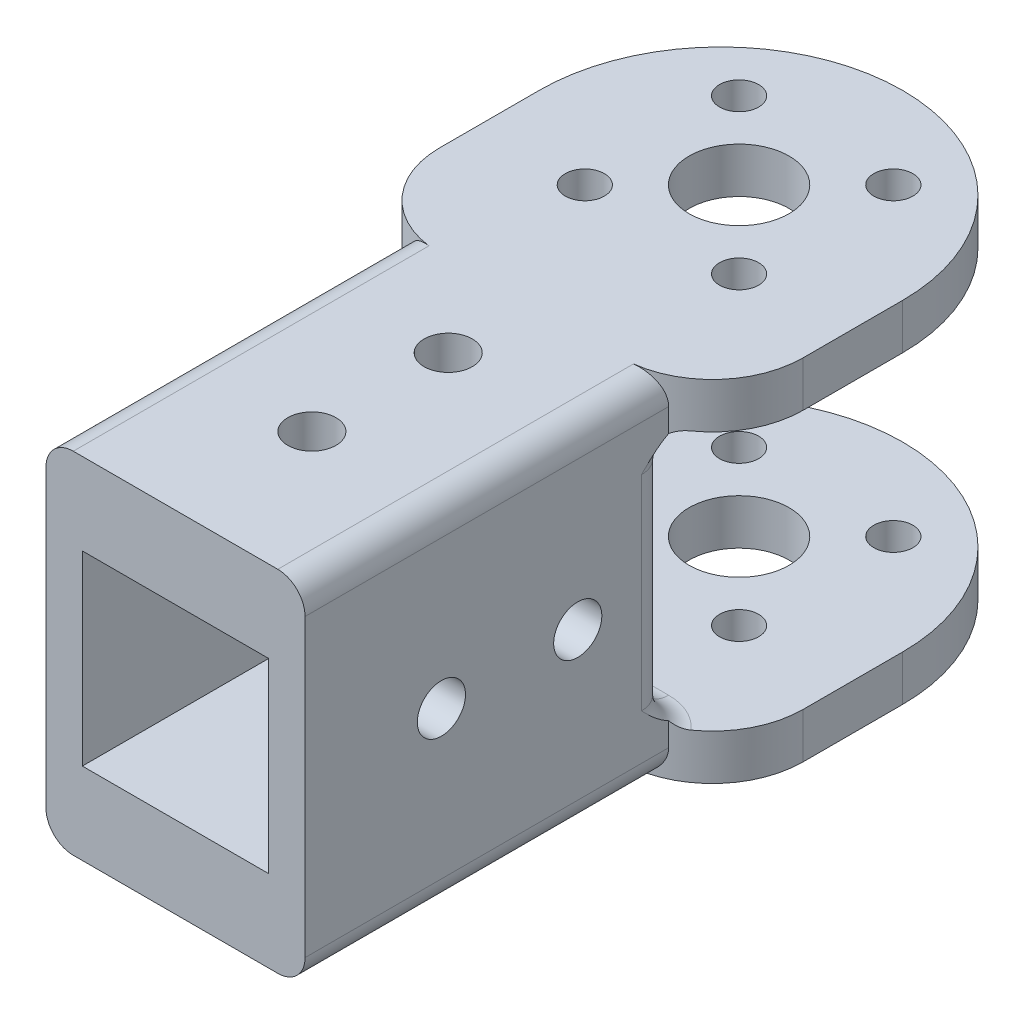
SolidWorks part; units mm, degrees
ref_plane "前视基准面" through (0, 0, 0) normal (0, 0, 1) x (1, 0, 0)
ref_plane "上视基准面" through (0, 0, 0) normal (0, 1, 0) x (1, 0, 0)
ref_plane "右视基准面" through (0, 0, 0) normal (1, 0, 0) x (0, 0, -1)
other "Configuration Table"
sketch "草图1" plane through (0, 0, 0) normal (0, 1, 0) x (1, 0, 0)
  circle A0 centre (0, 0) radius 17.5
  dimension "D1" = 35
extrude "凸台-拉伸4" add sketch "草图1" along normal blind 6
sketch "草图4" plane through (0, 6, 0) normal (0, 1, 0) x (1, 0, 0)
  line L1 (-20, -20) -> (20, -20)
  line L2 (-20, -20) -> (-20, 20)
  line L3 (-20, 20) -> (20, 20)
  line L4 (20, -20) -> (20, 20)
  line L5 (-20, -20) -> (20, 20) construction
  line L6 (-20, 20) -> (20, -20) construction
  point P0 (0, 0)
  dimension "D1" = 40
  dimension "D2" = 40
extrude "凸台-拉伸5" add sketch "草图4" along normal blind 30
fillet "圆角1" radius 5 1 edges at (0, 6, 17.5)
sketch "草图5" plane through (0, 0, 20) normal (0, 0, 1) x (1, 0, 0)
  line L0 (-1020, 21) -> (48980, 21) construction
  line L1 (-20, 36) -> (-20, 6) construction
  line L2 (0, -994) -> (0, 49006) construction
  line L3 (-10.3078, 6) -> (10.3078, 6) construction
  line L4 (-14.25, 35.25) -> (14.25, 35.25)
  line L5 (-10.25, 10.75) -> (10.25, 10.75)
  line L6 (-10.25, 10.75) -> (-10.25, 31.25)
  line L7 (-10.25, 31.25) -> (10.25, 31.25)
  line L8 (10.25, 10.75) -> (10.25, 31.25)
  line L9 (-10.25, 10.75) -> (10.25, 31.25) construction
  line L10 (-10.25, 31.25) -> (10.25, 10.75) construction
  line L11 (14.25, 6.75) -> (14.25, 35.25)
  line L12 (-14.25, 6.75) -> (14.25, 6.75)
  line L13 (-14.25, 6.75) -> (-14.25, 35.25)
  point P5 (-20, 21)
  point P6 (0, 21)
  point P10 (0, 6)
  dimension "D1" = 20.5
  dimension "D2" = 20.5
  dimension "D3" = 4
extrude "凸台-拉伸7" add sketch "草图5" along normal blind 40
sketch "草图7" plane through (0, 6.75, 0) normal (0, -1, 0) x (1, 0, 0)
  line L0 (0, 60) -> (0, 45)
  line L1 (-14.25, 60) -> (14.25, 60) construction
  line L2 (0, 45) -> (0, 30)
  circle A0 centre (0, 45) radius 2.65
  circle A1 centre (0, 30) radius 2.65
  dimension "D2" = 5.3
  dimension "D4" = 5.3
  dimension "D1" = 15
  dimension "D3" = 15
extrude "切除-拉伸1" cut sketch "草图7" against normal through all contours A1 | A0 region at (1.8208, 6.75, 31.8208)
sketch "草图8" plane through (14.25, 0, 0) normal (1, 0, 0) x (0, 0, -1)
  line L0 (-60, 21) -> (-45, 21)
  line L1 (-60, 6.75) -> (-60, 35.25) construction
  line L2 (-45, 21) -> (-30, 21)
  circle A0 centre (-45, 21) radius 2.65
  circle A1 centre (-30, 21) radius 2.65
  dimension "D2" = 5.3
  dimension "D4" = 5.3
  dimension "D1" = 15
  dimension "D3" = 15
extrude "切除-拉伸2" cut sketch "草图8" against normal through all contours L0 A0 L2 | A1 | A0 region at (14.25, 19.8753, 45)
sketch "草图26" plane through (0, 0, 0) normal (0, -1, 0) x (1, 0, 0)
  circle A0 centre (0, 0) radius 22.5
extrude "切除-拉伸15" cut sketch "草图26" against normal blind 6
sketch "草图27" plane through (0, 6, 0) normal (0, -1, 0) x (1, 0, 0)
  circle A0 centre (0, 0) radius 15
  dimension "D1" = 30
extrude "切除-拉伸16" cut sketch "草图27" against normal through all
sketch "草图28" plane through (0, 36, 0) normal (0, 1, 0) x (1, 0, 0)
  line L1 (-20, 20) -> (20, 20)
  line L2 (-20, 20) -> (-20, -20)
  line L3 (-20, -20) -> (20, -20)
  line L4 (20, 20) -> (20, -20)
extrude "切除-拉伸17" cut sketch "草图28" against normal blind 5
sketch "草图29" plane through (0, 6, 0) normal (0, -1, 0) x (1, 0, 0)
  line L1 (-20, 20) -> (20, 20)
  line L2 (-20, 20) -> (-20, -20)
  line L3 (-20, -20) -> (20, -20)
  line L4 (20, 20) -> (20, -20)
extrude "切除-拉伸18" cut sketch "草图29" against normal blind 5
sketch "草图30" plane through (0, 0, 20) normal (0, 0, -1) x (-1, 0, 0)
  line L1 (-14.25, 35.25) -> (14.25, 35.25)
  line L2 (-14.25, 35.25) -> (-14.25, 6.75)
  line L3 (-14.25, 6.75) -> (14.25, 6.75)
  line L4 (14.25, 35.25) -> (14.25, 6.75)
extrude "凸台-拉伸11" add sketch "草图30" against normal blind 5
sketch "草图31" plane through (0, 11, 0) normal (0, -1, 0) x (1, 0, 0)
  line L0 (0, 0) -> (0, -18)
  line L1 (0, -18) -> (8.3107, -12.4873)
  line L2 (8.3107, -12.4873) -> (-8.3107, -12.4873)
  line L3 (-8.3107, -12.4873) -> (0, -18)
  circle A0 centre (0, 0) radius 15 construction
  circle M8 centre (0, 0) radius 15
  dimension "D1" = 18
extrude "切除-拉伸19" cut sketch "草图31" against normal through all contours L3 L0 M8 | L0 L1 M8 region at (2.7702, 11, -14.3248) region at (-2.1466, 11, -15.6634)
fillet "圆角6" radius 20 4 edges at (-20, 21, -20) (20, 21, -20) (20, 21, 20) (-20, 21, 20)
ref_plane "基准面1" through (0, 21, 0) normal (0, 1, 0) x (1, 0, 0)
sketch "草图33" plane through (0, 21, 0) normal (0, 1, 0) x (1, 0, 0)
  circle A0 centre (0, 0) radius 20
  circle A1 centre (0, 0) radius 12.5
  dimension "D1" = 25
extrude "凸台-拉伸14" add sketch "草图33" along normal mid plane 2
sketch "草图36" plane through (0, 35.25, 0) normal (0, 1, 0) x (1, 0, 0)
  line L0 (14.25, -20) -> (-14.25, -20) construction
  line L1 (-14.25, -20) -> (14.25, -20)
  line L2 (-14.25, -20) -> (-14.25, -60)
  line L3 (-14.25, -60) -> (14.25, -60)
  line L4 (14.25, -20) -> (14.25, -60)
  line L5 (-14.25, -20) -> (14.25, -20) construction
  circle A0 centre (0, -30) radius 2.65
  circle A1 centre (0, -45) radius 2.65
extrude "凸台-拉伸15" add sketch "草图36" along normal mid plane 10
mirror "镜向1" about plane through (0, 21, 0) normal (0, 1, 0) of "凸台-拉伸15"
sketch "草图38" plane through (0, 0, 20) normal (0, 0, -1) x (-1, 0, 0)
  line L5 (-14.25, 40.25) -> (14.25, 40.25) construction
  line L6 (-20, 35.25) -> (20, 35.25)
  line L7 (-20, 35.25) -> (-20, 45.25)
  line L8 (-20, 45.25) -> (20, 45.25)
  line L9 (20, 35.25) -> (20, 45.25)
  line L10 (-20, 35.25) -> (20, 45.25) construction
  line L11 (-20, 45.25) -> (20, 35.25) construction
  line L12 (-1020, 40.25) -> (48980, 40.25)
  line L13 (-20, 40.25) -> (20, 40.25)
  point P0 (0, 40.25)
  point P10 (-20, 40.25)
  dimension "D1" = 10
  dimension "D2" = 40
extrude "凸台-拉伸16" add sketch "草图38" along normal blind 40 contours L12 L7 L6 L9 region at (0, 37.75, 20)
sketch "草图39" plane through (0, 11, 0) normal (0, -1, 0) x (1, 0, 0)
  line L1 (-20, -20) -> (20, -20)
  line L2 (-20, -20) -> (-20, 20)
  line L3 (-20, 20) -> (20, 20)
  line L4 (20, -20) -> (20, 20)
extrude "切除-拉伸20" cut sketch "草图39" against normal blind 20
mirror "镜向2" about plane through (0, 21, 0) normal (0, 1, 0) of "凸台-拉伸16"
sketch "草图40" plane through (0, 40.25, 0) normal (0, 1, 0) x (1, 0, 0)
  line L0 (0, 0) -> (0, 2)
  line L1 (-1000, 2) -> (49000, 2) construction
  line L2 (0, 2) -> (35355.3391, -35353.3391) construction
  circle A6 centre (0, 2) radius 5.5
  circle A8 centre (-8.4853, 10.4853) radius 2.15
  circle A9 centre (8.4853, 10.4853) radius 2.15
  circle A10 centre (8.4853, -6.4853) radius 2.15
  circle A11 centre (-8.4853, -6.4853) radius 2.15
  point P18 (0, 0)
  dimension "D1" = 2
  dimension "D5" = 4.3
  dimension "D6" = 4
  dimension "D2" = 11
  dimension "D4" = 45
extrude "切除-拉伸22" cut sketch "草图40" against normal through all contours A6 | A8 | A9 | A10 | A11 region at (-5.3444, 40.25, -2) region at (-8.4853, 40.25, -10.4853) region at (8.4853, 40.25, -10.4853) region at (8.4853, 40.25, 6.4853)
fillet "圆角11" radius 10 4 edges at (-20, 37.75, 20) (20, 37.75, 20) (20, 4.25, 20) (-20, 4.25, 20)
fillet "圆角12" radius 20 4 edges at (20, 4.25, -20) (-20, 4.25, -20) (-20, 37.75, -20) (20, 37.75, -20)
fillet "圆角13" radius 3 6 edges at (14.25, 21, 20) (-14.25, 21, 20) (-14.25, 40.25, 40) (14.25, 40.25, 40) (14.25, 1.75, 40) (-14.25, 1.75, 40)
fillet "圆角14" radius 3 6 edges at (13.3713, 6.75, 20.8787) (-13.3713, 6.75, 20.8787) (13.3713, 35.25, 20.8787) (-13.3713, 35.25, 20.8787) (0, 6.75, 20) (0, 35.25, 20)
sketch "草图42" plane through (0, 0, 60) normal (0, 0, 1) x (1, 0, 0)
  line L2 (-1003.4304, 21) -> (-1003.4304, 50021) construction
  line L4 (0, -998.25) -> (0, 49001.75) construction
  line L5 (-11.25, 1.75) -> (11.25, 1.75) construction
  line L6 (55, 21) -> (-55, 21) construction
  line L7 (-10.25, 10.75) -> (10.25, 10.75)
  line L8 (-10.25, 10.75) -> (-10.25, 31.25)
  line L9 (-10.25, 31.25) -> (10.25, 31.25)
  line L10 (10.25, 10.75) -> (10.25, 31.25)
  line L11 (-10.25, 10.75) -> (10.25, 31.25) construction
  line L12 (-10.25, 31.25) -> (10.25, 10.75) construction
  point P1 (0, 21)
  point P7 (0, 1.75)
  dimension "D1" = 20.5
  dimension "D2" = 20.5
extrude "切除-拉伸23" cut sketch "草图42" against normal blind 35
